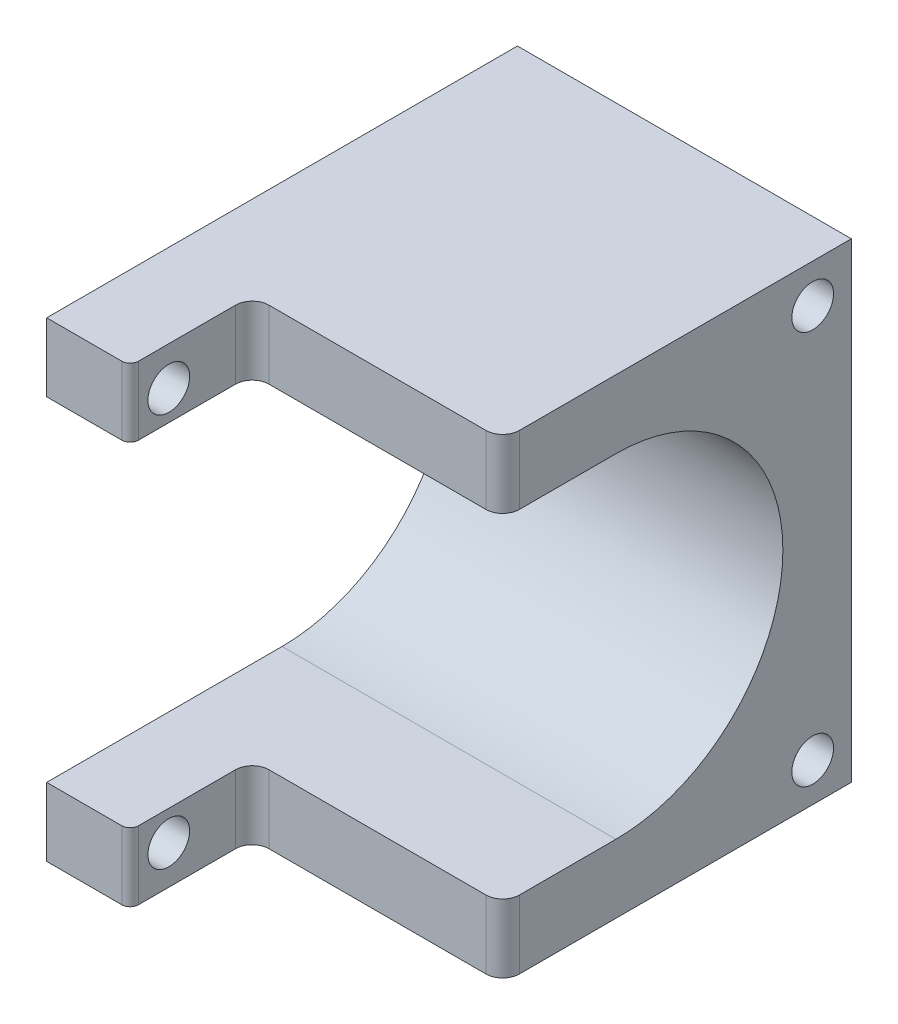
SolidWorks part; units mm, degrees
ref_plane "Front Plane" through (0, 0, 0) normal (0, 0, 1) x (1, 0, 0)
ref_plane "Top Plane" through (0, 0, 0) normal (0, 1, 0) x (1, 0, 0)
ref_plane "Right Plane" through (0, 0, 0) normal (1, 0, 0) x (0, 0, -1)
sketch "Sketch1" plane through (0, 0, 0) normal (1, 0, 0) x (0, 0, -1)
  line L1 (-17.4229, 1.4968) -> (38.9771, 1.4968)
  line L2 (-17.4229, 1.4968) -> (-17.4229, -54.9032)
  line L3 (-17.4229, -54.9032) -> (38.9771, -54.9032)
  line L4 (38.9771, 1.4968) -> (38.9771, -54.9032)
  dimension "D1" = 56.4
  dimension "D2" = 56.4
extrude "Boss-Extrude1" add sketch "Sketch1" along normal blind 40
sketch "Sketch2" plane through (40, 0, 0) normal (1, 0, 0) x (0, 0, -1)
  line L0 (10.7771, 1.4968) -> (10.7771, -54.9032) construction
  line L1 (38.9771, 1.4968) -> (-17.4229, 1.4968) construction
  line L2 (-17.4229, -54.9032) -> (38.9771, -54.9032) construction
  line L3 (-17.4229, -26.7032) -> (38.9771, -26.7032) construction
  line L4 (-17.4229, 1.4968) -> (-17.4229, -54.9032) construction
  line L5 (38.9771, -54.9032) -> (38.9771, 1.4968) construction
  circle A0 centre (-12.7929, -3.1332) radius 2.5
  circle A1 centre (-12.7929, -50.2732) radius 2.5
  circle A2 centre (34.3471, -3.1332) radius 2.5
  circle A3 centre (34.3471, -50.2732) radius 2.5
  dimension "D1" = 5
  dimension "D3" = 47.14
  dimension "D2" = 47.14
extrude "Cut-Extrude1" cut sketch "Sketch2" against normal through all
sketch "Sketch3" plane through (40, 0, 0) normal (1, 0, 0) x (0, 0, -1)
  line L0 (-17.4229, 1.4968) -> (-17.4229, -54.9032) construction
  line L1 (-17.4229, -8.1332) -> (29.3471, -8.1332)
  line L2 (-17.4229, -8.1332) -> (-17.4229, -45.2732)
  line L3 (-17.4229, -45.2732) -> (29.3471, -45.2732)
  line L4 (29.3471, -8.1332) -> (29.3471, -45.2732)
  line L5 (38.9771, -54.9032) -> (38.9771, 1.4968) construction
  circle A0 centre (-12.7929, -3.1332) radius 2.5 construction
  circle A1 centre (34.3471, -3.1332) radius 2.5 construction
  point P6 (29.3471, -26.7032)
  point P9 (38.9771, -26.7032)
  dimension "D1" = 5
  dimension "D2" = 5
extrude "Cut-Extrude2" [suppressed] cut sketch "Sketch3" against normal through all
sketch "Sketch4" plane through (40, 0, 0) normal (1, 0, 0) x (0, 0, -1)
  line L0 (38.9771, 1.4968) -> (-17.4229, 1.4968) construction
  line L1 (38.9771, -54.9032) -> (38.9771, 1.4968) construction
  line L2 (10.7771, -6.7032) -> (-17.4229, -6.7032)
  line L3 (-17.4229, 1.4968) -> (-17.4229, -54.9032) construction
  line L4 (10.7771, -46.7032) -> (-17.4229, -46.7032)
  line L5 (-17.4229, -46.7032) -> (-17.4229, -6.7032)
  arc A0 (10.7771, -46.7032) -> (10.7771, -6.7032) centre (10.7771, -26.7032) ccw
  point P5 (10.7771, 1.4968)
  point P9 (38.9771, -26.7032)
  dimension "D1" = 40
extrude "Cut-Extrude3" cut sketch "Sketch4" against normal through all
sketch "Sketch5" plane through (40, 0, 0) normal (1, 0, 0) x (0, 0, -1)
  line L0 (38.9771, 1.4968) -> (-17.4229, 1.4968) construction
  line L1 (-17.4229, -6.7032) -> (-2.7929, -6.7032)
  line L2 (-17.4229, -6.7032) -> (-17.4229, 1.4968)
  line L3 (-17.4229, 1.4968) -> (-2.7929, 1.4968)
  line L4 (-2.7929, -6.7032) -> (-2.7929, 1.4968)
  line L5 (38.9771, -26.7032) -> (30.7771, -26.7032) construction
  line L6 (38.9771, -54.9032) -> (38.9771, 1.4968) construction
  line L7 (-17.4229, -54.9032) -> (-2.7929, -54.9032)
  line L8 (-2.7929, -46.7032) -> (-2.7929, -54.9032)
  line L9 (-17.4229, -46.7032) -> (-2.7929, -46.7032)
  line L10 (-17.4229, -46.7032) -> (-17.4229, -54.9032)
  circle A2 centre (-12.7929, -3.1332) radius 2.5 construction
  arc A3 (10.7771, -46.7032) -> (10.7771, -6.7032) centre (10.7771, -26.7032) ccw construction
  point P7 (-12.7929, -3.1332)
  dimension "D1" = 10
extrude "Cut-Extrude4" cut sketch "Sketch5" against normal offset from surface (30 mm away) 10 up to face at (0, -50.2732, 15.2929)
fillet "Fillet1" radius 2 2 edges at (10, -50.8032, 2.7929) (10, -2.6032, 2.7929)
fillet "Fillet2" radius 2 2 edges at (40, -50.8032, 2.7929) (40, -2.6032, 2.7929)
fillet "Fillet3" radius 1 2 edges at (10, -50.8032, 17.4229) (10, -2.6032, 17.4229)
